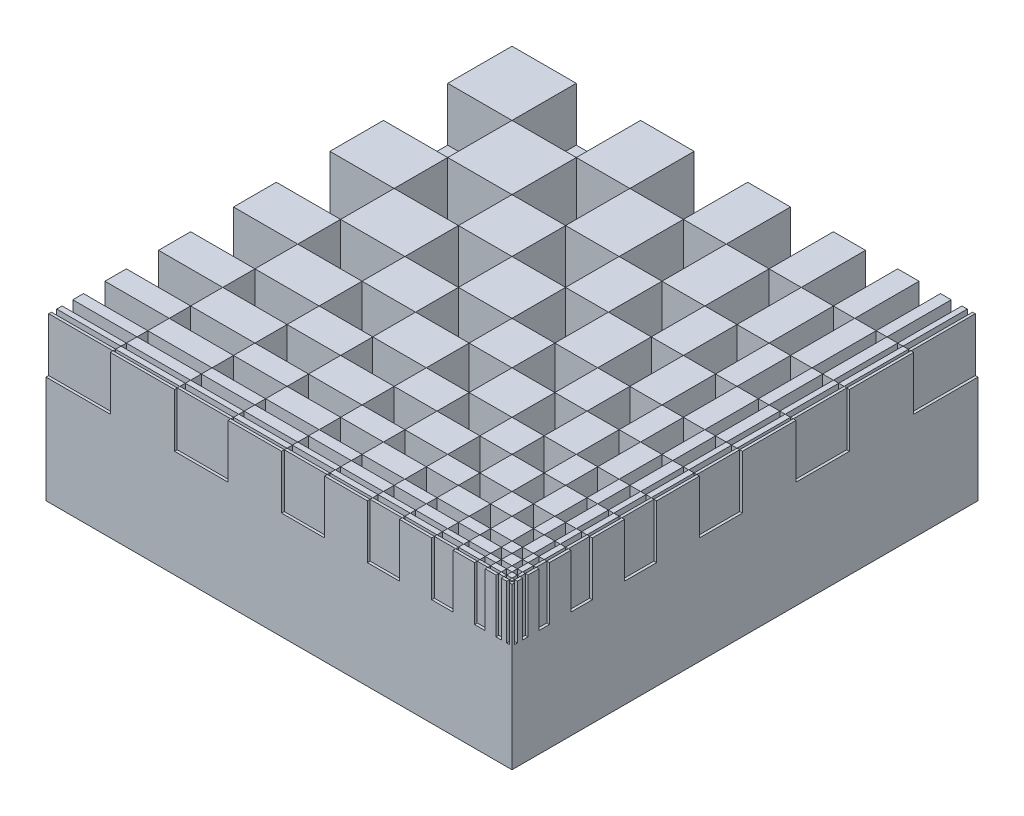
SolidWorks part; units mm, degrees
ref_plane "Front Plane" through (0, 0, 0) normal (0, 0, 1) x (1, 0, 0)
ref_plane "Top Plane" through (0, 0, 0) normal (0, 1, 0) x (1, 0, 0)
ref_plane "Right Plane" through (0, 0, 0) normal (1, 0, 0) x (0, 0, -1)
sketch "Sketch1" plane through (0, 0, 0) normal (0, 1, 0) x (1, 0, 0)
  line L0 (0, 0) -> (1.2, -1.2) construction
  line L1 (0, 0) -> (1.2, 0)
  line L2 (0, 0) -> (0, -1.2)
  line L3 (0, -1.2) -> (1.2, -1.2)
  line L4 (1.2, 0) -> (1.2, -1.2)
  line L5 (1.2, -4.3) -> (1.2, -4.35)
  line L6 (0, -4.35) -> (1.2, -4.35)
  line L7 (1.2, 0) -> (2.2, 0)
  line L8 (1.2, 0) -> (1.2, -1.2)
  line L9 (1.2, -1.2) -> (2.2, -1.2)
  line L10 (2.2, 0) -> (2.2, -1.2)
  line L11 (2.2, 0) -> (3, 0)
  line L12 (2.2, 0) -> (2.2, -1.2)
  line L13 (2.2, -1.2) -> (3, -1.2)
  line L14 (3, 0) -> (3, -1.2)
  line L15 (3, 0) -> (3.6, 0)
  line L16 (3, 0) -> (3, -1.2)
  line L17 (3, -1.2) -> (3.6, -1.2)
  line L18 (3.6, 0) -> (3.6, -1.2)
  line L19 (3.6, 0) -> (4, 0)
  line L20 (3.6, 0) -> (3.6, -1.2)
  line L21 (3.6, -1.2) -> (4, -1.2)
  line L22 (4, 0) -> (4, -1.2)
  line L23 (4, 0) -> (4.2, 0)
  line L24 (4, 0) -> (4, -1.2)
  line L25 (4, -1.2) -> (4.2, -1.2)
  line L26 (4.2, 0) -> (4.2, -1.2)
  line L27 (4.2, 0) -> (4.3, 0)
  line L28 (4.2, 0) -> (4.2, -1.2)
  line L29 (4.2, -1.2) -> (4.3, -1.2)
  line L30 (4.3, 0) -> (4.3, -1.2)
  line L31 (4.3, 0) -> (4.35, 0)
  line L32 (4.3, 0) -> (4.3, -1.2)
  line L33 (4.3, -1.2) -> (4.35, -1.2)
  line L34 (4.35, 0) -> (4.35, -1.2)
  line L35 (0, -4.3) -> (0, -4.35)
  line L36 (0, -4.3) -> (1.2, -4.3)
  line L37 (1.2, -4.2) -> (1.2, -4.3)
  line L38 (0, -4.3) -> (1.2, -4.3)
  line L39 (0, -4.2) -> (0, -4.3)
  line L40 (0, -4.2) -> (1.2, -4.2)
  line L41 (1.2, -4) -> (1.2, -4.2)
  line L42 (0, -4.2) -> (1.2, -4.2)
  line L43 (0, -4) -> (0, -4.2)
  line L44 (0, -4) -> (1.2, -4)
  line L45 (1.2, -3.6) -> (1.2, -4)
  line L46 (0, -4) -> (1.2, -4)
  line L47 (0, -3.6) -> (0, -4)
  line L48 (0, -3.6) -> (1.2, -3.6)
  line L49 (1.2, -3) -> (1.2, -3.6)
  line L50 (0, -3.6) -> (1.2, -3.6)
  line L51 (0, -3) -> (0, -3.6)
  line L52 (0, -3) -> (1.2, -3)
  line L53 (1.2, -2.2) -> (1.2, -3)
  line L54 (0, -3) -> (1.2, -3)
  line L55 (0, -2.2) -> (0, -3)
  line L56 (0, -2.2) -> (1.2, -2.2)
  line L57 (1.2, -1.2) -> (1.2, -2.2)
  line L58 (0, -2.2) -> (1.2, -2.2)
  line L59 (0, -1.2) -> (0, -2.2)
  line L60 (0, -1.2) -> (1.2, -1.2)
  line L61 (2.2, -1.2) -> (2.2, -4.35)
  line L62 (3, -1.2) -> (3, -4.35)
  line L63 (1.2, -4.35) -> (4.35, -4.35)
  line L64 (4.35, -1.2) -> (4.35, -4.35)
  line L65 (1.2, -2.2) -> (4.35, -2.2)
  line L66 (1.2, -3) -> (4.35, -3)
  line L67 (1.2, -3.6) -> (4.35, -3.6)
  line L68 (1.2, -4) -> (4.35, -4)
  line L69 (1.2, -4.2) -> (4.35, -4.2)
  line L70 (1.2, -4.3) -> (4.35, -4.3)
  line L71 (3.6, -1.2) -> (3.6, -4.35)
  line L72 (4, -1.2) -> (4, -4.35)
  line L73 (4.2, -1.2) -> (4.2, -4.35)
  line L74 (4.3, -1.2) -> (4.3, -4.35)
  line L75 (0.6, 0) -> (0.6, -4.35)
  line L76 (1.7, 0) -> (1.7, -4.35)
  line L77 (2.6, 0) -> (2.6, -4.35)
  line L78 (3.3, 0) -> (3.3, -4.35)
  line L79 (3.8, 0) -> (3.8, -4.35)
  line L80 (4.1, 0) -> (4.1, -4.35)
  line L81 (4.25, 0) -> (4.25, -4.35)
  line L82 (4.325, 0) -> (4.325, -4.35)
  line L83 (0, -0.6) -> (4.35, -0.6)
  line L84 (0, -1.7) -> (4.35, -1.7)
  line L85 (0, -2.6) -> (4.35, -2.6)
  line L86 (0, -3.3) -> (4.35, -3.3)
  line L87 (0, -3.8) -> (4.35, -3.8)
  line L88 (0, -4.1) -> (4.35, -4.1)
  line L89 (0, -4.25) -> (4.35, -4.25)
  line L90 (0, -4.325) -> (4.35, -4.325)
  dimension "D1" = 1.2
  dimension "D2" = 1.2
  dimension "D3" = 1
  dimension "D4" = 0.8
  dimension "D5" = 0.6
  dimension "D6" = 0.4
  dimension "D7" = 0.2
  dimension "D8" = 0.1
  dimension "D9" = 0.05
sketch "Sketch2" plane through (0, 0, 0) normal (0, 1, 0) x (1, 0, 0)
  line L1 (0, 0) -> (4.35, 0)
  line L2 (0, 0) -> (0, -4.35)
  line L3 (0, -4.35) -> (4.35, -4.35)
  line L4 (4.35, 0) -> (4.35, -4.35)
extrude "Boss-Extrude1" add sketch "Sketch2" along normal mid plane 1
extrude "Boss-Extrude4" add sketch "Sketch1" along normal blind 0.5 from surface contours L4 L83 L76 L7 | L1 L0 L75 | L0 L2 L83 | L57 L84 L76 L9 | L61 L84 L77 L13 | L10 L83 L77 L11 | L14 L83 L78 L15 | L62 L84 L78 L17 | L71 L84 L79 L21 | L18 L83 L79 L19 | L22 L83 L80 L23 | L72 L84 L80 L25 | L26 L83 L81 L27 | L30 L83 L82 L31 | L73 L84 L81 L29 | L74 L84 L82 L33 | L61 L85 L77 L65 | L62 L86 L78 L66 | L71 L87 L79 L67 | L62 L85 L78 L65 | L71 L85 L79 L65 | L71 L86 L79 L66 | L72 L86 L80 L66 | L72 L85 L80 L65 | L73 L85 L81 L65 | L73 L86 L81 L66 | L72 L87 L80 L67 | L73 L87 L81 L67 | L74 L85 L82 L65 | L74 L86 L82 L66 | L74 L87 L82 L67 | L72 L88 L80 L68 | L73 L88 L81 L68 | L73 L89 L81 L69 | L74 L88 L82 L68 | L74 L89 L82 L69 | L74 L90 L82 L70 region at (0.4, 0, 0.2) region at (0.2, 0, 0.4) region at (1.45, 0, 1.45) region at (1.45, 0, 0.3) region at (2.4, 0, 1.45) region at (2.4, 0, 0.3) region at (3.15, 0, 1.45) region at (2.4, 0, 2.4) region at (3.15, 0, 0.3) region at (3.7, 0, 1.45) region at (3.15, 0, 2.4) region at (3.7, 0, 0.3) region at (4.05, 0, 1.45) region at (3.7, 0, 2.4) region at (3.15, 0, 3.15) region at (4.05, 0, 0.3) region at (4.225, 0, 1.45) region at (4.05, 0, 2.4) region at (3.7, 0, 3.15) region at (4.225, 0, 0.3) region at (4.3125, 0, 1.45) region at (4.225, 0, 2.4) region at (4.05, 0, 3.15) region at (3.7, 0, 3.7) region at (4.3125, 0, 0.3) region at (4.3125, 0, 2.4) region at (4.225, 0, 3.15) region at (4.05, 0, 3.7) region at (4.3125, 0, 3.15) region at (4.225, 0, 3.7) region at (4.05, 0, 4.05) region at (4.3125, 0, 3.7) region at (4.225, 0, 4.05) region at (4.3125, 0, 4.05) region at (4.225, 0, 4.225) region at (4.3125, 0, 4.225) region at (4.3125, 0, 4.3125) starting at face at (2.175, 0.5, 2.175)
extrude "Boss-Extrude6" add sketch "Sketch1<6>" along normal blind 0.5 from surface separate body contours L83 L0 L8 | L0 L75 L60 | L83 L76 L9 L12 | L84 L76 L65 L61 | L84 L77 L65 L62 | L83 L77 L13 L16 | L83 L78 L17 L20 | L84 L78 L65 L71 | L84 L79 L65 L72 | L83 L79 L21 L24 | L83 L80 L25 L28 | L83 L81 L29 L32 | L83 L82 L33 L34 | L84 L80 L65 L73 | L84 L81 L65 L74 | L84 L82 L65 L64 | L85 L82 L66 L64 | L85 L81 L66 L74 | L85 L80 L66 L73 | L85 L79 L66 L72 | L85 L78 L66 L71 | L85 L77 L66 L62 | L86 L78 L67 L71 | L86 L79 L67 L72 | L87 L79 L68 L72 | L87 L80 L68 L73 | L86 L80 L67 L73 | L86 L81 L67 L74 | L87 L81 L68 L74 | L86 L82 L67 L64 | L87 L82 L68 L64 | L88 L80 L69 L73 | L88 L81 L69 L74 | L89 L81 L70 L74 | L89 L82 L70 L64 | L88 L82 L69 L64 | L90 L82 L63 L64 region at (1, 0, 0.8) region at (0.8, 0, 1) region at (1.95, 0, 0.9) region at (1.95, 0, 1.95) region at (2.8, 0, 0.9) region at (2.8, 0, 1.95) region at (3.45, 0, 0.9) region at (3.45, 0, 1.95) region at (2.8, 0, 2.8) region at (3.9, 0, 0.9) region at (3.9, 0, 1.95) region at (3.45, 0, 2.8) region at (4.15, 0, 0.9) region at (4.15, 0, 1.95) region at (3.9, 0, 2.8) region at (3.45, 0, 3.45) region at (4.275, 0, 0.9) region at (4.275, 0, 1.95) region at (4.15, 0, 2.8) region at (3.9, 0, 3.45) region at (4.3375, 0, 0.9) region at (4.3375, 0, 1.95) region at (4.275, 0, 2.8) region at (4.15, 0, 3.45) region at (3.9, 0, 3.9) region at (4.3375, 0, 2.8) region at (4.275, 0, 3.45) region at (4.15, 0, 3.9) region at (4.3375, 0, 3.45) region at (4.275, 0, 3.9) region at (4.15, 0, 4.15) region at (4.3375, 0, 3.9) region at (4.275, 0, 4.15) region at (4.3375, 0, 4.15) region at (4.275, 0, 4.275) region at (4.3375, 0, 4.275) region at (4.3375, 0, 4.3375) starting at face at (3.0309, 0.5, 0.5382)
sketch "Sketch1<6>" plane through (0, 0, 0) normal (0, 1, 0) x (1, 0, 0) same geometry as "Sketch1"
ref_plane "Plane1" through (0, 0, 0) normal (-0.7071, 0, 0.7071) x (0.7071, 0, 0.7071)
sketch "Sketch3" plane through (0, 0, 0) normal (0, 1, 0) x (1, 0, 0)
  circle A0 centre (0.6, -0.6) radius 0.0001
  circle A1 centre (1.2, -0.6) radius 0
  circle A2 centre (1.2, -1.2) radius 0
  circle A3 centre (1.7, -1.2) radius 0
  circle A4 centre (1.7, -1.7) radius 0
  circle A5 centre (1.7, -0.6) radius 0
  circle A6 centre (2.2, -0.6) radius 0.0001
  circle A7 centre (2.6, -0.6) radius 0.0001
  circle A8 centre (3, -0.6) radius 0.0001
  circle A9 centre (3.3, -0.6) radius 0.0001
  circle A10 centre (3.6, -0.6) radius 0.0001
  circle A11 centre (3.8, -0.6) radius 0.0001
  circle A12 centre (4, -0.6) radius 0
  circle A13 centre (4.1, -0.6) radius 0
  circle A14 centre (4.2, -0.6) radius 0
  circle A15 centre (4.25, -0.6) radius 0
  circle A16 centre (4.3, -0.6) radius 0
  circle A17 centre (4.325, -0.6) radius 0
  circle A18 centre (4.325, -1.2) radius 0
  circle A19 centre (4.3, -1.2) radius 0
  circle A20 centre (4.25, -1.2) radius 0
  circle A21 centre (4.2, -1.2) radius 0
  circle A22 centre (4.1, -1.2) radius 0
  circle A23 centre (4, -1.2) radius 0
  circle A24 centre (3.8, -1.2) radius 0.0001
  circle A25 centre (3.6, -1.2) radius 0.0001
  circle A26 centre (2.2, -1.2) radius 0.0001
  circle A27 centre (2.6, -1.2) radius 0.0001
  circle A28 centre (3, -1.2) radius 0.0001
  circle A29 centre (3.3, -1.2) radius 0.0001
  circle A30 centre (2.2, -1.7) radius 0.0001
  circle A31 centre (2.6, -1.7) radius 0.0001
  circle A32 centre (3, -1.7) radius 0.0001
  circle A33 centre (3.3, -1.7) radius 0.0001
  circle A34 centre (3.6, -1.7) radius 0.0001
  circle A35 centre (3.8, -1.7) radius 0.0001
  circle A36 centre (4, -1.7) radius 0
  circle A37 centre (4.1, -1.7) radius 0
  circle A38 centre (4.2, -1.7) radius 0
  circle A39 centre (4.25, -1.7) radius 0
  circle A40 centre (4.3, -1.7) radius 0
  circle A41 centre (4.325, -1.7) radius 0
  circle A42 centre (2.2, -2.2) radius 0.0001
  circle A43 centre (2.6, -2.2) radius 0.0001
  circle A44 centre (2.6, -2.6) radius 0.0001
  circle A45 centre (3, -2.6) radius 0.0001
  circle A46 centre (3, -2.2) radius 0.0001
  circle A47 centre (3.3, -2.2) radius 0.0001
  circle A48 centre (3.6, -2.2) radius 0.0001
  circle A49 centre (3.8, -2.2) radius 0.0001
  circle A50 centre (3.6, -2.6) radius 0.0001
  circle A51 centre (3.3, -2.6) radius 0.0001
  circle A52 centre (3.3, -3) radius 0.0001
  circle A53 centre (3, -3) radius 0.0001
  circle A54 centre (3.3, -3.3) radius 0.0001
  circle A55 centre (3.6, -3) radius 0.0001
  circle A56 centre (3.6, -3.3) radius 0.0001
  circle A57 centre (3.6, -3.6) radius 0.0001
  circle A58 centre (3.8, -3.6) radius 0.0001
  circle A59 centre (3.8, -3.8) radius 0.0001
  circle A60 centre (3.8, -2.6) radius 0.0001
  circle A61 centre (3.8, -3) radius 0.0001
  circle A62 centre (3.8, -3.3) radius 0.0001
  circle A63 centre (4, -2.2) radius 0
  circle A64 centre (4, -2.6) radius 0
  circle A65 centre (4, -3) radius 0
  circle A66 centre (4, -3.3) radius 0
  circle A67 centre (4, -3.6) radius 0
  circle A68 centre (4, -3.8) radius 0
  circle A69 centre (4, -4) radius 0
  circle A70 centre (4.2, -2.2) radius 0
  circle A71 centre (4.25, -2.2) radius 0
  circle A72 centre (4.3, -2.2) radius 0
  circle A73 centre (4.325, -2.2) radius 0
  circle A74 centre (4.1, -2.2) radius 0
  circle A75 centre (4.1, -2.6) radius 0
  circle A76 centre (4.2, -2.6) radius 0
  circle A77 centre (4.25, -2.6) radius 0
  circle A78 centre (4.3, -2.6) radius 0
  circle A79 centre (4.325, -2.6) radius 0
  circle A80 centre (4.325, -3) radius 0
  circle A81 centre (4.3, -3) radius 0
  circle A82 centre (4.25, -3) radius 0
  circle A83 centre (4.2, -3) radius 0
  circle A84 centre (4.2, -3.3) radius 0
  circle A85 centre (4.1, -3) radius 0
  circle A86 centre (4.1, -3.3) radius 0
  circle A87 centre (4.25, -3.3) radius 0
  circle A88 centre (4.3, -3.3) radius 0
  circle A89 centre (4.325, -3.3) radius 0
  circle A90 centre (4.1, -3.6) radius 0
  circle A91 centre (4.2, -3.6) radius 0
  circle A92 centre (4.25, -3.6) radius 0
  circle A93 centre (4.3, -3.6) radius 0
  circle A94 centre (4.325, -3.6) radius 0
  circle A95 centre (4.325, -3.8) radius 0
  circle A96 centre (4.3, -3.8) radius 0
  circle A97 centre (4.25, -3.8) radius 0
  circle A98 centre (4.2, -3.8) radius 0
  circle A99 centre (4.1, -3.8) radius 0
  circle A100 centre (4.1, -4) radius 0
  circle A101 centre (4.2, -4) radius 0
  circle A102 centre (4.25, -4) radius 0
  circle A103 centre (4.3, -4) radius 0
  circle A104 centre (4.325, -4) radius 0
  circle A105 centre (4.325, -4.1) radius 0
  circle A106 centre (4.3, -4.1) radius 0
  circle A107 centre (4.25, -4.1) radius 0
  circle A108 centre (4.2, -4.1) radius 0
  circle A109 centre (4.1, -4.1) radius 0
  circle A110 centre (4.2, -4.2) radius 0
  circle A111 centre (4.25, -4.2) radius 0
  circle A112 centre (4.3, -4.2) radius 0
  circle A113 centre (4.325, -4.2) radius 0
  circle A114 centre (4.325, -4.25) radius 0
  circle A115 centre (4.3, -4.25) radius 0
  circle A116 centre (4.325, -4.3) radius 0
  circle A117 centre (4.3, -4.3) radius 0
  circle A118 centre (4.325, -4.325) radius 0
  circle A119 centre (4.25, -4.25) radius 0
  dimension "D1" = 0.0001
extrude "Boss-Extrude7" add sketch "Sketch3" along normal blind 0.5 from surface starting at face at (3.0309, 0.5, 0.5382)
mirror "Mirror4" [suppressed] about plane through (0, 0, 0) normal (-0.7071, 0, 0.7071)
mirror "Mirror7" [suppressed] about plane through (0, 0, 0) normal (-0.7071, 0, 0.7071) of bodies 168 104 106 108 107 109 110 111 112 113 114 115 116 117 118 119 120 121 122 125 127 128 129 130 131 132 134 136 137
mirror "Mirror10" about plane through (0, 0, 0) normal (-0.7071, 0, 0.7071) of bodies 168
equation "\"D3@Sketch1\"=\"D1@Sketch1\"-.2"
equation "\"D4@Sketch1\"=\"D3@Sketch1\"-.2"
equation "\"D5@Sketch1\"=\"D4@Sketch1\"-.2"
equation "\"D6@Sketch1\"=\"D5@Sketch1\"-.2"
equation "\"D7@Sketch1\"=\"D6@Sketch1\"-.2"
